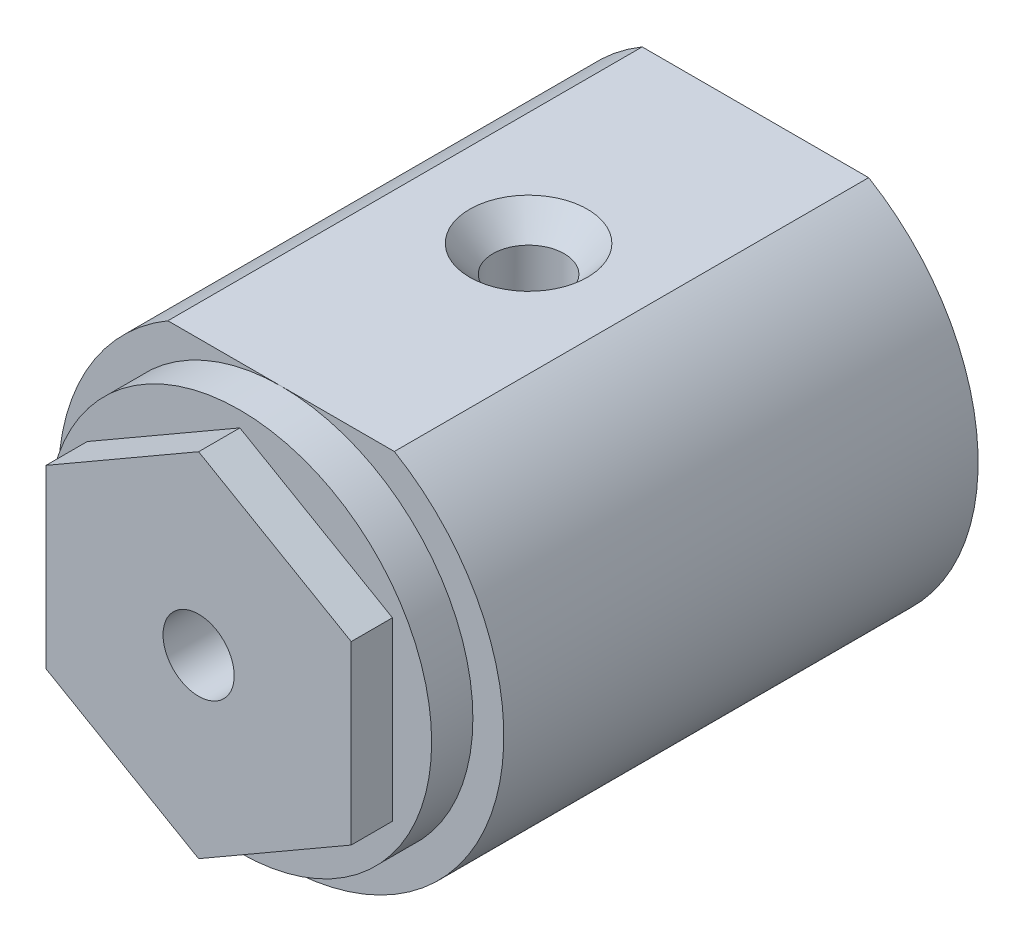
SolidWorks part; units mm, degrees
ref_plane "Front Plane" through (0, 0, 0) normal (0, 0, 1) x (1, 0, 0)
ref_plane "Top Plane" through (0, 0, 0) normal (0, 1, 0) x (1, 0, 0)
ref_plane "Right Plane" through (0, 0, 0) normal (1, 0, 0) x (0, 0, -1)
sketch "Base" plane through (0, 0, 0) normal (0, 0, 1) x (1, 0, 0)
  line L0 (-5.2154, 5.8) -> (5.2154, 5.8)
  line L1 (-5.4909, 9.3) -> (5.4909, 9.3)
  arc A0 (-5.4909, 9.3) -> (5.4909, 9.3) centre (0, 0) ccw
  arc A1 (-5.2154, 5.8) -> (5.2154, 5.8) centre (0, 0) ccw
  point P6 (0, -7.8)
  dimension "D1" = 10.8
  dimension "D2" = 3.5
  dimension "D4" = 7.8
  dimension "D3" = 13.6
extrude "Boss-Extrude1" add sketch "Base" along normal blind 23
ref_plane "Chamfer Plane" through (0, 9.3, 0) normal (0, 1, 0) x (1, 0, 0)
sketch "Screw Hole" plane through (0, 9.3, 0) normal (0, 1, 0) x (1, 0, 0)
  line L0 (5.4909, 0) -> (-5.4909, 0) construction
  circle A0 centre (0, -11) radius 1.8
  point P2 (0, 0)
  dimension "D1" = 3.6
  dimension "D2" = 11
hole_wizard "CSK for #4 Flat Head Machine Screw1" positions "Sketch4" profile "Sketch3" countersink size "#4" standard "ANSI Inch" end condition up to next
sketch "Sketch4" plane through (0, 9.3, 0) normal (0, 1, 0) x (1, 0, 0)
  point P0 (0, -11)
sketch "Sketch3" plane through (0, 9.3, 11) normal (1, 0, 0) x (0, 0, 1)
  line L0 (0, 0) -> (0, 3.5)
  line L1 (0, 3.5) -> (1.7272, 3.5)
  line L2 (1.7272, 3.5) -> (1.7272, 1.3003)
  line L3 (1.7272, 1.3003) -> (2.8575, 0)
  line L5 (2.8575, 0) -> (0, 0)
  line L6 (-1.7272, 1.3003) -> (-2.8575, 0) construction
  line L11 (0, -6.35) -> (0, 107.95) construction
  dimension "Thru Hole Dia." = 3.4544
  dimension "Thru Hole Depth" = 3.5
  dimension "Near C'Sink Dia." = 5.715
  dimension "Near C'Sink Angle" = 82
ref_plane "Plane1" through (0, 0, 23) normal (0, 0, 1) x (1, 0, 0)
sketch "Sketch5" plane through (0, 0, 23) normal (0, 0, 1) x (1, 0, 0)
  circle A0 centre (0, 0) radius 9.3
extrude "Boss-Extrude2" add sketch "Sketch5" along normal blind 2 and the other way blind 4
ref_plane "Plane2" through (0, 0, 25) normal (0, 0, 1) x (1, 0, 0)
sketch "Sketch6" plane through (0, 0, 25) normal (0, 0, 1) x (1, 0, 0)
  line L1 (0, 8.5448) -> (-7.4, 4.2724)
  line L2 (-7.4, 4.2724) -> (-7.4, -4.2724)
  line L3 (-7.4, -4.2724) -> (0, -8.5448)
  line L4 (0, -8.5448) -> (7.4, -4.2724)
  line L5 (7.4, -4.2724) -> (7.4, 4.2724)
  line L6 (7.4, 4.2724) -> (0, 8.5448)
  circle A0 centre (0, 0) radius 7.4 construction
  dimension "D1" = 14.8
extrude "Boss-Extrude3" add sketch "Sketch6" along normal blind 2
ref_plane "Plane3" through (0, 0, 19) normal (0, 0, -1) x (-1, 0, 0)
sketch "Sketch7" plane through (0, 0, 19) normal (0, 0, -1) x (-1, 0, 0)
  line L1 (0, 3.8682) -> (-3.35, 1.9341)
  line L2 (-3.35, 1.9341) -> (-3.35, -1.9341)
  line L3 (-3.35, -1.9341) -> (0, -3.8682)
  line L4 (0, -3.8682) -> (3.35, -1.9341)
  line L5 (3.35, -1.9341) -> (3.35, 1.9341)
  line L6 (3.35, 1.9341) -> (0, 3.8682)
  circle A0 centre (0, 0) radius 3.35 construction
  dimension "D1" = 6.7
extrude "Cut-Extrude1" cut sketch "Sketch7" against normal blind 3.6
sketch "Sketch8" plane through (0, 0, 19) normal (0, 0, -1) x (-1, 0, 0)
  circle A0 centre (0, 0) radius 1.725
  dimension "D1" = 3.45
extrude "Cut-Extrude2" cut sketch "Sketch8" against normal through all
